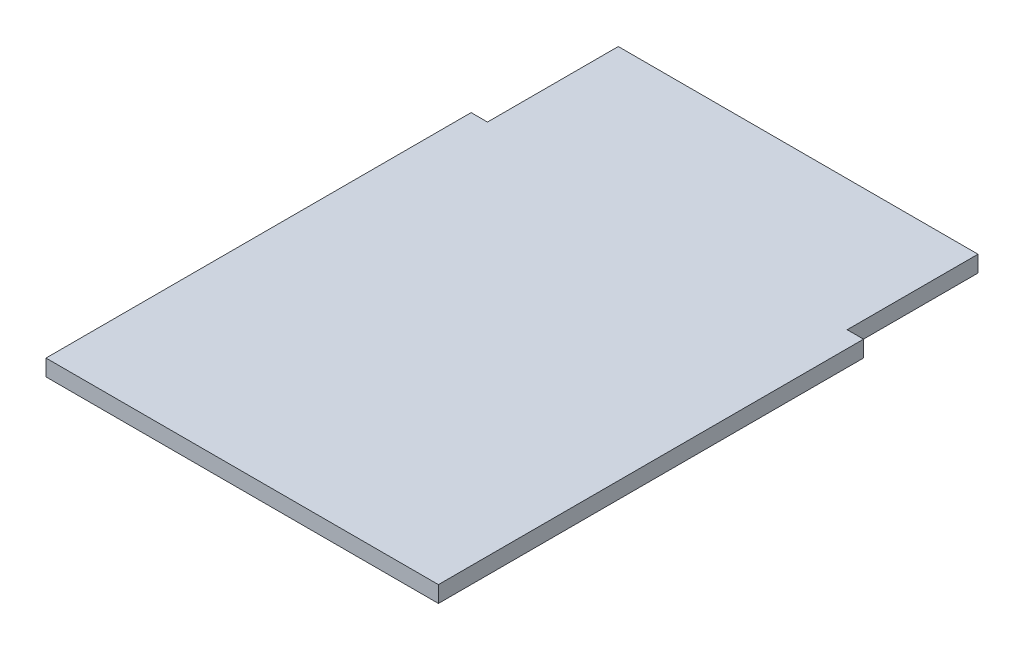
SolidWorks part; units mm, degrees
ref_plane "Front Plane" through (0, 0, 0) normal (0, 0, 1) x (1, 0, 0)
ref_plane "Top Plane" through (0, 0, 0) normal (0, 1, 0) x (1, 0, 0)
ref_plane "Right Plane" through (0, 0, 0) normal (1, 0, 0) x (0, 0, -1)
sketch "Sketch1" plane through (0, 0, 0) normal (0, 1, 0) x (1, 0, 0)
  line L0 (-6.35, 0) -> (-6.35, -50.8)
  line L1 (-6.35, 0) -> (-146.05, 0)
  line L2 (0, -50.8) -> (0, -215.9)
  line L3 (0, -215.9) -> (-152.4, -215.9)
  line L4 (-152.4, -50.8) -> (-152.4, -215.9)
  line L5 (-6.35, -50.8) -> (0, -50.8)
  line L6 (-146.05, 0) -> (-146.05, -50.8)
  line L7 (-146.05, -50.8) -> (-152.4, -50.8)
  point P7 (-3.175, -50.8)
  dimension "D1" = 152.4
  dimension "D2" = 215.9
  dimension "D3" = 50.8
  dimension "D4" = 6.35
  dimension "D5" = 6.35
  dimension "D6" = 50.8
extrude "Boss-Extrude1" add sketch "Sketch1" along normal blind 6.35
